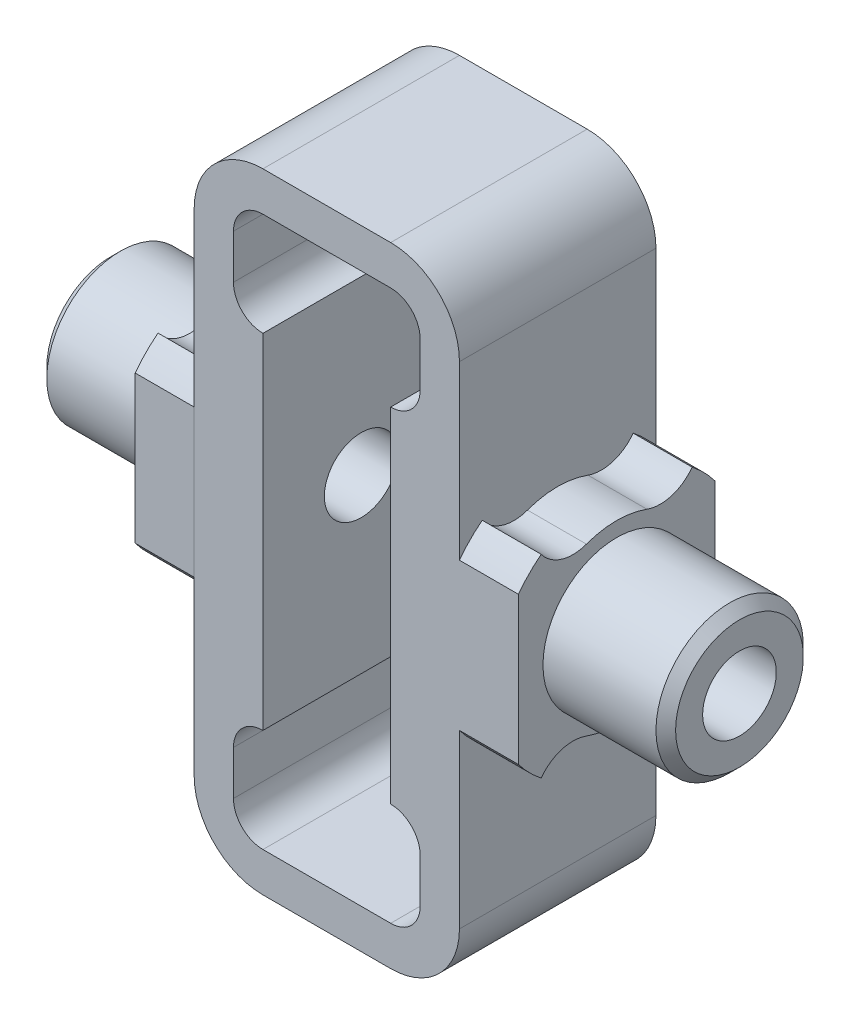
SolidWorks part; units mm, degrees
ref_plane "Front Plane" through (0, 0, 0) normal (0, 0, 1) x (1, 0, 0)
ref_plane "Top Plane" through (0, 0, 0) normal (0, 1, 0) x (1, 0, 0)
ref_plane "Right Plane" through (0, 0, 0) normal (1, 0, 0) x (0, 0, -1)
sketch "Sketch1" plane through (0, 0, 0) normal (0, 0, 1) x (1, 0, 0)
  line L0 (0, -64) -> (0, 64) construction
  line L1 (0, 64) -> (-13, 64)
  line L2 (-27, 50) -> (-27, -50)
  line L3 (-13, -64) -> (0, -64)
  line L4 (0, 64) -> (0, -64)
  arc A0 (-27, -50) -> (-13, -64) centre (-13, -50) ccw
  arc A1 (-13, 64) -> (-27, 50) centre (-13, 50) ccw
  point P9 (0, 80.0019)
  dimension "D1" = 14
  dimension "D2" = 27
  dimension "D3" = 128
extrude "Boss-Extrude1" add sketch "Sketch1" along normal blind 20 and the other way blind 20
sketch "Sketch2" plane through (0, 0, 20) normal (0, 0, 1) x (1, 0, 0)
  line L0 (-13, 35) -> (-13, -35)
  line L4 (0, -64) -> (0, 64) construction
  line L5 (0, -56) -> (0, 56)
  line L6 (0, 56) -> (-13, 56)
  line L7 (-19, 50) -> (-19, 41)
  line L10 (0, 64) -> (-13, 64) construction
  line L11 (0, 0) -> (-27, 0) construction
  line L12 (-27, 50) -> (-27, -50) construction
  line L13 (-19, -50) -> (-19, -41)
  line L14 (0, -56) -> (-13, -56)
  arc A1 (-13, 56) -> (-19, 50) centre (-13, 50) ccw
  arc A2 (-19, 41) -> (-13, 35) centre (-13, 41) ccw
  arc A3 (-19, -41) -> (-13, -35) centre (-13, -41) cw
  arc A4 (-13, -56) -> (-19, -50) centre (-13, -50) cw
  point P2 (-13, 0)
  point P24 (0, 0)
  point P25 (0, 0)
  point P26 (0, 0)
  dimension "D2" = 6
  dimension "D5" = 6
  dimension "D1" = 13
  dimension "D3" = 70
  dimension "D4" = 8
  dimension "D6" = 19
extrude "Cut-Extrude1" cut sketch "Sketch2" against normal blind 40
mirror "Mirror1" about plane through (0, 0, 0) normal (1, 0, 0) of "Boss-Extrude1", "Cut-Extrude1"
sketch "Sketch4" plane through (-27, 0, 0) normal (-1, 0, 0) x (0, 0, 1)
  line L0 (0, 64) -> (0, -64) construction
  line L1 (-20, 64) -> (20, 64) construction
  line L2 (-20, -64) -> (20, -64) construction
  line L3 (20, 0) -> (-20, 0) construction
  line L4 (20, 50) -> (20, -50) construction
  line L5 (-20, 50) -> (-20, -50) construction
  line L6 (20, 15) -> (20, -15)
  line L7 (-20, 15) -> (-20, -15)
  line L8 (-6.1564, 16.9145) -> (0, 0) construction
  line L9 (0, 0) -> (6.1564, 16.9145) construction
  arc A0 (20, 15) -> (15.3607, 19.7243) centre (0, 0) ccw
  arc A1 (6.1564, 16.9145) -> (-6.1564, 16.9145) centre (0, 0) ccw
  arc A2 (6.1564, 16.9145) -> (15.3607, 19.7243) centre (8.8925, 24.432) ccw
  arc A3 (-20, -15) -> (-15.3607, -19.7243) centre (0, 0) ccw
  arc A4 (-6.1564, 16.9145) -> (-15.3607, 19.7243) centre (-8.8925, 24.432) cw
  arc A5 (-15.3607, 19.7243) -> (-20, 15) centre (0, 0) ccw
  arc A6 (-6.1564, -16.9145) -> (6.1564, -16.9145) centre (0, 0) ccw
  arc A7 (-6.1564, -16.9145) -> (-15.3607, -19.7243) centre (-8.8925, -24.432) ccw
  arc A8 (6.1564, -16.9145) -> (15.3607, -19.7243) centre (8.8925, -24.432) cw
  arc A9 (15.3607, -19.7243) -> (20, -15) centre (0, 0) ccw
  point P25 (14.8835, 20.0869)
  point P26 (15.4818, 19.6294)
  dimension "D1" = 50
  dimension "D2" = 36
  dimension "D3" = 8
  dimension "D4" = 40
extrude "Boss-Extrude2" add sketch "Sketch4" along normal blind 12 separate body
sketch "Sketch5" plane through (-39, 0, 0) normal (-1, 0, 0) x (0, 0, 1)
  circle A0 centre (0, 0) radius 15
  dimension "D1" = 30
extrude "Boss-Extrude3" add sketch "Sketch5" along normal blind 25
hole_wizard "Ø15.0 (15) Diameter Hole1" positions "3DSketch1" profile "Sketch7" hole size "Ø15.0" standard "ANSI Metric"
sketch3d "3DSketch1"
  circle A0 centre (-64, 0, 0) radius 15 construction
  point P0 (-64, 0, 0)
  point P7 (-79, 0, 0)
sketch "Sketch7" plane through (-64, 0, 0) normal (0, 1, 0) x (0, 0, 1)
  line L0 (0, 0) -> (0, 55.5065)
  line L1 (0, 55.5065) -> (7.5, 51)
  line L2 (7.5, 51) -> (7.5, 0)
  line L5 (7.5, 0) -> (0, 0)
  line L10 (0, 55.5065) -> (-7.5, 51) construction
  line L11 (0, -6.35) -> (0, 107.95) construction
  dimension "Hole Dia." = 15
  dimension "Hole Depth" = 51
  dimension "Drill Angle" = 118
chamfer "Chamfer1" distance 2 angle 45 1 edges at (-64, 0, 15)
mirror "Mirror2" about plane through (0, 0, 0) normal (1, 0, 0) of "Ø15.0 (15) Diameter Hole1", "Boss-Extrude3", "Boss-Extrude2", "Chamfer1"
